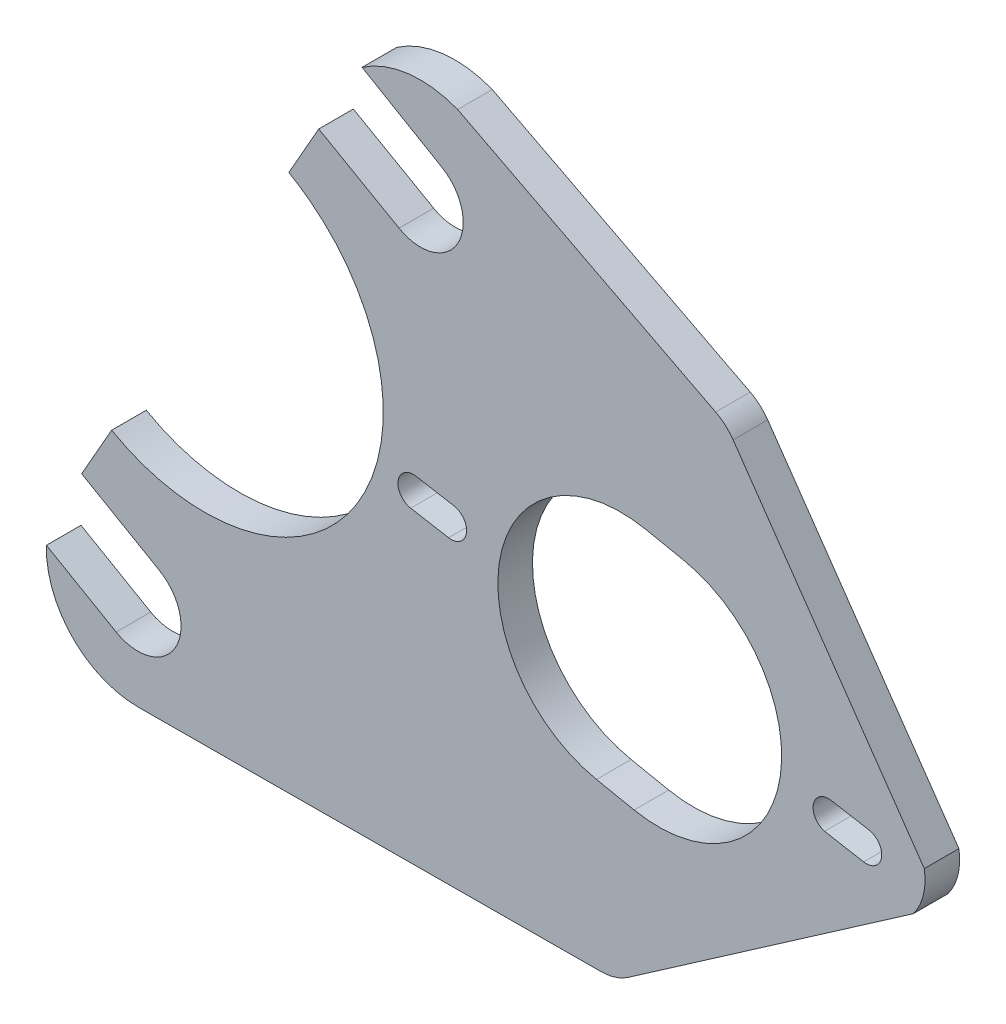
SolidWorks part; units mm, degrees
ref_plane "Front Plane" through (0, 0, 0) normal (0, 0, 1) x (1, 0, 0)
ref_plane "Top Plane" through (0, 0, 0) normal (0, 1, 0) x (1, 0, 0)
ref_plane "Right Plane" through (0, 0, 0) normal (1, 0, 0) x (0, 0, -1)
sketch "Model" plane through (0, 0, 0) normal (0, 0, 1) x (1, 0, 0)
  line L0 (135.7866, 62.5287) -> (131.8474, 63.2232)
  line L1 (59.7829, 35.593) -> (65.7308, 35.6231)
  line L2 (78.5552, 97.0562) -> (86.904, 92.2982)
  line L4 (83.0608, 104.8605) -> (91.3561, 100.0093)
  line L5 (75.44, 91.5752) -> (78.5552, 97.0562)
  line L6 (61.9848, 49.0002) -> (53.897, 53.6704)
  line L7 (53.897, 53.6704) -> (57.0121, 59.1515)
  line L8 (50.2285, 45.3956) -> (57.481, 41.2084)
  line L9 (107.8791, 35.8363) -> (113.8271, 35.8664)
  line L10 (65.7308, 35.6231) -> (107.8791, 35.8363)
  line L11 (116.4435, 77.205) -> (112.5231, 77.9992)
  line L12 (135.2289, 59.3776) -> (131.1616, 60.1004)
  line L13 (92.6109, 70.1416) -> (88.6717, 70.8362)
  line L14 (92.0552, 66.9902) -> (88.116, 67.6848)
  line L15 (111.3606, 52.1146) -> (107.4403, 52.9088)
  line L16 (143.1744, 59.6379) -> (139.0962, 35.8664)
  line L17 (113.8271, 35.8664) -> (139.0962, 35.8664)
  line L18 (92.9995, 106.0361) -> (143.1744, 59.6379)
  arc A0 (57.481, 41.2084) -> (61.9848, 49.0002) centre (59.7329, 45.1043) ccw
  arc A1 (86.904, 92.2982) -> (91.3561, 100.0093) centre (89.13, 96.1538) ccw
  arc A2 (111.3606, 52.1146) -> (116.4435, 77.205) centre (113.9021, 64.6598) ccw
  arc A4 (92.9995, 106.0361) -> (83.0608, 104.8605) centre (89.1296, 96.154) ccw
  arc A5 (50.2285, 45.3956) -> (59.7829, 35.593) centre (59.7348, 45.1036) ccw
  arc A6 (112.5231, 77.9992) -> (107.4403, 52.9088) centre (109.9817, 65.454) ccw
  arc A7 (131.8474, 63.2232) -> (131.4196, 60.0545) centre (131.5696, 61.6475) ccw
  arc A8 (88.729, 70.825) -> (88.116, 67.6848) centre (88.3938, 69.2605) ccw
  arc A9 (92.0552, 66.9902) -> (92.6109, 70.1416) centre (92.3331, 68.5659) ccw
  arc A10 (135.2289, 59.3776) -> (135.7866, 62.5287) centre (135.5088, 60.953) ccw
  ellipse E1 centre (66.2261, 75.3633) end of major axis (82.8916, 65.8915) minor radius 18.6473 (57.0121, 59.1515) -> (75.44, 91.5752) ccw
  point P42 (106.1748, 87.0422)
  point P43 (131.5661, 69.2597)
  point P44 (113.7866, 43.8663)
  point P45 (88.3952, 61.6488)
  point P46 (89.1296, 96.154)
  dimension "D1" = 3.2
  dimension "D2" = 3.2
  dimension "D3" = 3.2
  dimension "D4" = 4
  dimension "D5" = 4
extrude "Boss-Extrude1" add sketch "Model" along normal blind 3.6 contours A6 | L12 A10 L0 A7 | L14 A9 L13 A8 | L16 L17 L9 L10 L1 A5 L8 A0 L6 L7 E1 L5 L2 A1 L4 A4 L18 region at (133.5397, 61.301, 0) region at (111.9419, 65.0569, 0) region at (90.3635, 68.9132, 0)
sketch "Sketch1" plane through (0, 0, 0) normal (0, 0, -1) x (-1, 0, 0)
  line L0 (-111.0378, 36.9372) -> (-140.869, 57.6203) construction
  line L1 (-111.0378, 36.9372) -> (-140.869, 57.6203)
  line L2 (-140.869, 57.6203) -> (-151.0149, 64.6548)
  line L3 (-151.0149, 64.6548) -> (-139.1687, 25.7481)
  line L4 (-139.1687, 25.7481) -> (-100.6908, 27.009)
  line L5 (-100.6908, 27.009) -> (-96.8976, 27.1333)
  line L6 (-111.0378, 36.9372) -> (-96.8976, 27.1333)
extrude "Cut-Extrude1" cut sketch "Sketch1" against normal blind 10
sketch "Sketch2" plane through (0, 0, 3.6) normal (0, 0, 1) x (1, 0, 0)
  line L1 (143.0928, 59.1621) -> (143.3344, 59.3296)
  line L2 (141.6251, 61.795) -> (143.1638, 59.5758)
  line L3 (120.942, 91.6262) -> (92.9995, 106.0361)
  line L4 (120.942, 91.6262) -> (143.3344, 59.3296)
  line L10 (109.4616, 35.8443) -> (143.0928, 59.1621)
  line L11 (143.0928, 59.1621) -> (143.1744, 59.6379)
  line L12 (143.1744, 59.6379) -> (92.9995, 106.0361)
  line L13 (83.0608, 104.8605) -> (91.3561, 100.0093)
  line L14 (86.904, 92.2982) -> (78.5552, 97.0562)
  line L15 (78.5552, 97.0562) -> (75.44, 91.5752)
  line L16 (57.0121, 59.1515) -> (53.897, 53.6704)
  line L17 (53.897, 53.6704) -> (61.9848, 49.0002)
  line L18 (57.481, 41.2084) -> (50.2285, 45.3956)
  line L19 (59.7829, 35.593) -> (109.4616, 35.8443)
  line L23 (83.0608, 104.8605) -> (91.3561, 100.0093)
  line L24 (86.904, 92.2982) -> (78.5552, 97.0562)
  line L25 (78.5552, 97.0562) -> (75.44, 91.5752)
  line L26 (57.0121, 59.1515) -> (53.897, 53.6704)
  line L27 (53.897, 53.6704) -> (61.9848, 49.0002)
  line L28 (57.481, 41.2084) -> (50.2285, 45.3956)
  line L29 (59.7829, 35.593) -> (109.4616, 35.8443)
  arc A4 (92.9995, 106.0361) -> (83.0608, 104.8605) centre (89.1296, 96.154) ccw
  arc A5 (86.904, 92.2982) -> (91.3561, 100.0093) centre (89.13, 96.1538) ccw
  arc A6 (57.481, 41.2084) -> (61.9848, 49.0002) centre (59.7329, 45.1043) ccw
  arc A7 (50.2285, 45.3956) -> (59.7829, 35.593) centre (59.7348, 45.1036) ccw
  arc A8 (92.9995, 106.0361) -> (83.0608, 104.8605) centre (89.1296, 96.154) ccw
  arc A9 (86.904, 92.2982) -> (91.3561, 100.0093) centre (89.13, 96.1538) ccw
  arc A10 (57.481, 41.2084) -> (61.9848, 49.0002) centre (59.7329, 45.1043) ccw
  arc A11 (50.2285, 45.3956) -> (59.7829, 35.593) centre (59.7348, 45.1036) ccw
  ellipse E1 centre (66.2261, 75.3633) end of major axis (82.8916, 65.8915) minor radius 18.6473 (57.0121, 59.1515) -> (75.44, 91.5752) ccw
  ellipse E2 centre (66.2261, 75.3633) end of major axis (82.8916, 65.8915) minor radius 18.6473 (57.0121, 59.1515) -> (75.44, 91.5752) ccw
  line M18 (143.1744, 59.6379) -> (92.9995, 106.0361)
  dimension "D1" = 0
extrude "Boss-Extrude2" add sketch "Sketch2" against normal blind 3.6 contours L3 L2 M18 region at (118.9887, 85.8129, 3.6)
fillet "Fillet2" radius 5 1 edges at (109.4616, 35.8443, 1.8)
fillet "Fillet3" radius 5 1 edges at (120.942, 91.6262, 1.8)
sketch "Sketch4" plane through (0, 0, 0) normal (0, 0, -1) x (-1, 0, 0)
  line L0 (-139.7366, 65.3566) -> (-145.7221, 59.6101)
  line L1 (-145.7221, 59.6101) -> (-139.7366, 56.5493)
  arc A0 (-139.7366, 65.3566) -> (-139.7366, 56.5493) centre (-135.5088, 60.953) ccw
extrude "Cut-Extrude4" cut sketch "Sketch4" against normal blind 10 contours L0 L1 A0
